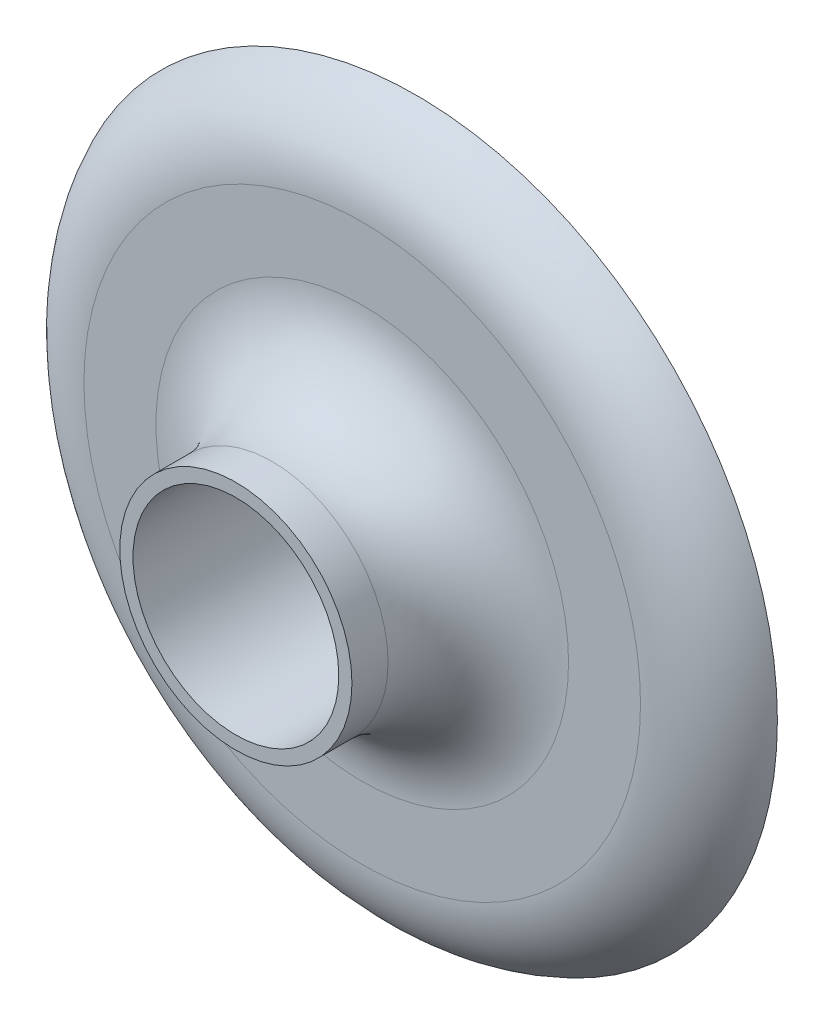
SolidWorks part; units mm, degrees
ref_plane "Front" through (0, 0, 0) normal (0, 0, 1) x (1, 0, 0)
ref_plane "Top" through (0, 0, 0) normal (0, 1, 0) x (1, 0, 0)
ref_plane "Right" through (0, 0, 0) normal (1, 0, 0) x (0, 0, -1)
sketch "Sketch1" plane through (0, 0, 0) normal (0, 0, 1) x (1, 0, 0)
  circle A0 centre (-23.323, 24.1353) radius 50.8
  dimension "D1" = 101.6
extrude "Boss-Extrude1" add sketch "Sketch1" along normal blind 25.4
sketch "Sketch2" plane through (0, 0, 25.4) normal (0, 0, 1) x (1, 0, 0)
  line L0 (-23.323, 74.9353) -> (-23.323, -26.6647) construction
  line L1 (-23.323, -26.6647) -> (-23.323, 24.1353) construction
  circle A0 centre (-23.323, 24.1353) radius 50.8 construction
  circle A1 centre (-23.323, 24.1353) radius 14.478
  dimension "D1" = 28.956
extrude "Cut-Extrude1" cut sketch "Sketch2" against normal blind 25.4
sketch "Sketch3" plane through (0, 0, 25.4) normal (0, 0, 1) x (1, 0, 0)
  circle A0 centre (-23.323, 24.1353) radius 16.3331
extrude "Cut-Extrude2" cut sketch "Sketch3" along direction (0, 0, 1) on the side against the normal blind 17.78 flip side to cut
fillet "Fillet1" radius 12.7 1 edges at (-6.99, 24.1353, 7.62)
fillet "Fillet2" radius 12.7 1 edges at (27.477, 24.1353, 7.62)
